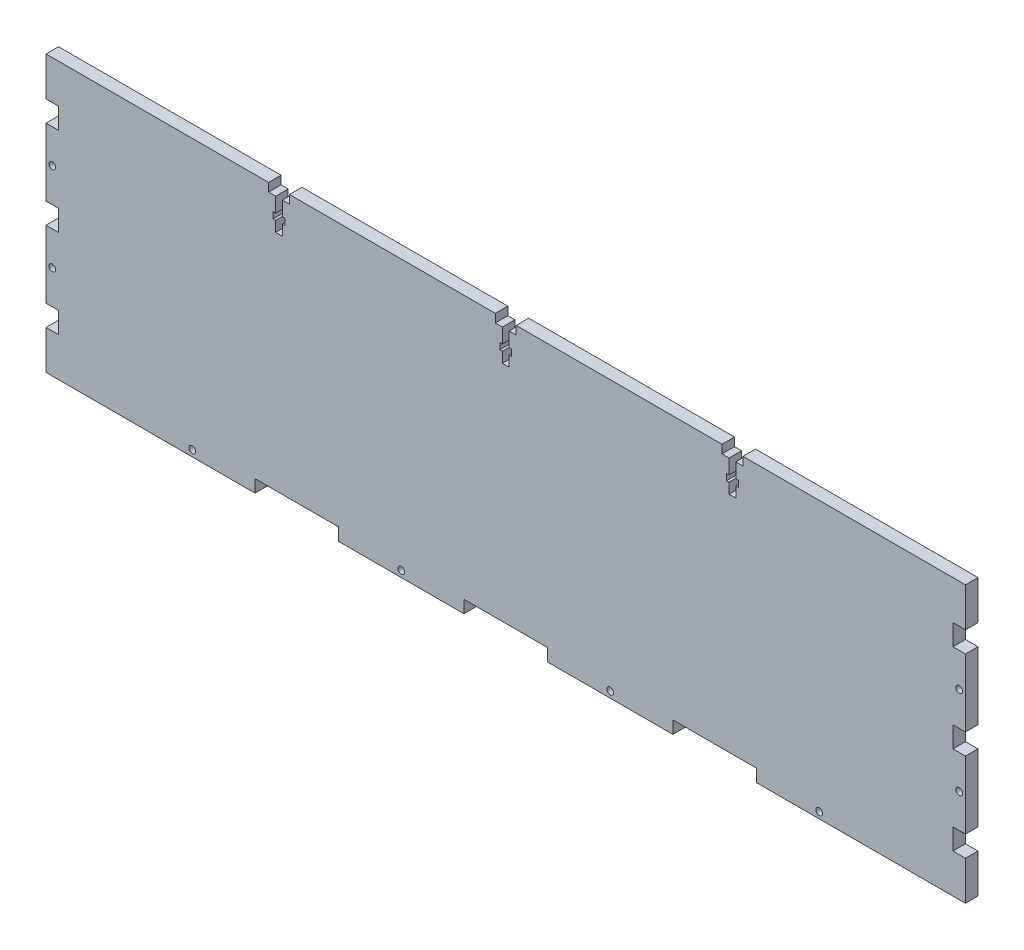
SolidWorks part; units mm, degrees
ref_plane "Front Plane" through (0, 0, 0) normal (0, 0, 1) x (1, 0, 0)
ref_plane "Top Plane" through (0, 0, 0) normal (0, 1, 0) x (1, 0, 0)
ref_plane "Right Plane" through (0, 0, 0) normal (1, 0, 0) x (0, 0, -1)
sketch "Sketch1" plane through (0, 0, 0) normal (0, 0, 1) x (1, 0, 0)
  line L1 (-220, -66) -> (220, -66)
  line L2 (-220, -66) -> (-220, 66)
  line L3 (-220, 66) -> (220, 66)
  line L4 (220, -66) -> (220, 66)
  line L5 (-220, -66) -> (220, 66) construction
  line L6 (-220, 66) -> (220, -66) construction
  point P0 (0, 0)
  dimension "D1" = 440
  dimension "D2" = 132
extrude "Boss-Extrude1" add sketch "Sketch1" along normal blind 6
sketch "Sketch2" plane through (0, 0, 0) normal (0, 0, -1) x (-1, 0, 0)
  line L0 (220, 47.3321) -> (220, 37.3321) construction
  line L1 (220, 37.3321) -> (214, 37.3321) construction
  line L2 (214, 37.3321) -> (214, 47.3321) construction
  line L3 (214, 47.3321) -> (220, 47.3321) construction
  line L12 (220, -37.3321) -> (220, -47.3321) construction
  line L13 (220, -47.3321) -> (214, -47.3321) construction
  line L14 (214, -47.3321) -> (214, -37.3321) construction
  line L15 (214, -37.3321) -> (220, -37.3321) construction
  line L16 (220, 47.3321) -> (220, 37.3321)
  line L17 (220, 37.3321) -> (214, 37.3321)
  line L18 (214, 37.3321) -> (214, 47.3321)
  line L19 (214, 47.3321) -> (220, 47.3321)
  line L20 (220, -37.3321) -> (220, -47.3321)
  line L21 (220, -47.3321) -> (214, -47.3321)
  line L22 (214, -47.3321) -> (214, -37.3321)
  line L23 (214, -37.3321) -> (220, -37.3321)
  line L24 (-214, -37.3321) -> (-214, -47.3321) construction
  line L25 (-214, -47.3321) -> (-220, -47.3321) construction
  line L26 (-220, -47.3321) -> (-220, -37.3321) construction
  line L27 (-220, -37.3321) -> (-214, -37.3321) construction
  line L28 (-214, 47.3321) -> (-214, 37.3321) construction
  line L29 (-214, 37.3321) -> (-220, 37.3321) construction
  line L30 (-220, 37.3321) -> (-220, 47.3321) construction
  line L31 (-220, 47.3321) -> (-214, 47.3321) construction
  line L32 (-214, -37.3321) -> (-214, -47.3321)
  line L33 (-214, -47.3321) -> (-220, -47.3321)
  line L34 (-220, -47.3321) -> (-220, -37.3321)
  line L35 (-220, -37.3321) -> (-214, -37.3321)
  line L36 (-214, 47.3321) -> (-214, 37.3321)
  line L37 (-214, 37.3321) -> (-220, 37.3321)
  line L38 (-220, 37.3321) -> (-220, 47.3321)
  line L39 (-220, 47.3321) -> (-214, 47.3321)
  line L44 (220, -5) -> (220, 5)
  line L45 (214, -5) -> (220, -5)
  line L46 (214, 5) -> (214, -5)
  line L47 (220, 5) -> (214, 5)
  line L48 (220, -5) -> (220, 5)
  line L49 (214, -5) -> (220, -5)
  line L50 (214, 5) -> (214, -5)
  line L51 (220, 5) -> (214, 5)
  line L52 (-214, -5) -> (-214, 5)
  line L53 (-220, -5) -> (-214, -5)
  line L54 (-220, 5) -> (-220, -5)
  line L55 (-214, 5) -> (-220, 5)
  line L56 (-214, -5) -> (-214, 5)
  line L57 (-220, -5) -> (-214, -5)
  line L58 (-220, 5) -> (-220, -5)
  line L59 (-214, 5) -> (-220, 5)
  circle A0 centre (217, 21.1661) radius 1.6 construction
  circle A1 centre (217, -21.1661) radius 1.6 construction
  circle A2 centre (-217, 21.1661) radius 1.6 construction
  circle A3 centre (-217, -21.1661) radius 1.6 construction
  circle A4 centre (217, 21.1661) radius 1.6
  circle A5 centre (217, -21.1661) radius 1.6
  circle A6 centre (-217, 21.1661) radius 1.6
  circle A7 centre (-217, -21.1661) radius 1.6
  dimension "D2" = 0
  dimension "D3" = 0
extrude "Cut-Extrude1" cut sketch "Sketch2" against normal up to next
sketch "Sketch3" plane through (0, 0, 0) normal (0, 0, -1) x (-1, 0, 0)
  circle A0 centre (-150, -63) radius 1.6 construction
  circle A1 centre (-50, -63) radius 1.6 construction
  circle A2 centre (50, -63) radius 1.6 construction
  circle A3 centre (150, -63) radius 1.6 construction
  circle A4 centre (-150, -63) radius 1.6
  circle A5 centre (-50, -63) radius 1.6
  circle A6 centre (50, -63) radius 1.6
  circle A7 centre (150, -63) radius 1.6
extrude "Cut-Extrude2" cut sketch "Sketch3" against normal up to next
sketch "Sketch4" plane through (0, 0, 0) normal (0, 0, -1) x (-1, 0, 0)
  line L0 (80, -66) -> (120, -66) construction
  line L1 (120, -66) -> (120, -60) construction
  line L2 (120, -60) -> (80, -60) construction
  line L3 (80, -60) -> (80, -66) construction
  line L4 (-20, -66) -> (20, -66) construction
  line L5 (20, -66) -> (20, -60) construction
  line L6 (20, -60) -> (-20, -60) construction
  line L7 (-20, -60) -> (-20, -66) construction
  line L8 (-120, -66) -> (-80, -66) construction
  line L9 (-80, -66) -> (-80, -60) construction
  line L10 (-80, -60) -> (-120, -60) construction
  line L11 (-120, -60) -> (-120, -66) construction
  line L12 (80, -66) -> (120, -66)
  line L13 (120, -66) -> (120, -60)
  line L14 (120, -60) -> (80, -60)
  line L15 (80, -60) -> (80, -66)
  line L16 (-20, -66) -> (20, -66)
  line L17 (20, -66) -> (20, -60)
  line L18 (20, -60) -> (-20, -60)
  line L19 (-20, -60) -> (-20, -66)
  line L20 (-120, -66) -> (-80, -66)
  line L21 (-80, -66) -> (-80, -60)
  line L22 (-80, -60) -> (-120, -60)
  line L23 (-120, -60) -> (-120, -66)
extrude "Cut-Extrude3" cut sketch "Sketch4" against normal up to next
sketch "Sketch5" plane through (0, 66, 0) normal (0, 1, 0) x (1, 0, 0)
  line L0 (220, 0) -> (-220, 0) construction
  line L1 (-113.5, -6) -> (-103.5, -6)
  line L2 (-113.5, -6) -> (-113.5, 0)
  line L3 (-113.5, 0) -> (-103.5, 0)
  line L4 (-103.5, -6) -> (-103.5, 0)
  line L5 (-113.5, -6) -> (-103.5, 0) construction
  line L6 (-113.5, 0) -> (-103.5, -6) construction
  line L7 (-103.5, -6) -> (-103.5, 0) construction
  line L8 (5, -6) -> (5, 0) construction
  line L9 (-5, -6) -> (5, -6)
  line L10 (-5, -6) -> (-5, 0)
  line L11 (-5, 0) -> (5, 0)
  line L12 (5, -6) -> (5, 0)
  line L13 (-5, -6) -> (5, 0) construction
  line L14 (-5, 0) -> (5, -6) construction
  line L15 (113.5, -6) -> (113.5, 0) construction
  line L16 (103.5, -6) -> (113.5, -6)
  line L17 (103.5, -6) -> (103.5, 0)
  line L18 (103.5, 0) -> (113.5, 0)
  line L19 (113.5, -6) -> (113.5, 0)
  line L20 (103.5, -6) -> (113.5, 0) construction
  line L21 (103.5, 0) -> (113.5, -6) construction
  point P0 (-108.5, -3)
  point P10 (0, -3)
  point P18 (108.5, -3)
extrude "Cut-Extrude4" cut sketch "Sketch5" against normal blind 4
sketch "Sketch6" plane through (0, 0, 0) normal (0, 0, -1) x (-1, 0, 0)
  line L0 (-108.5, 62) -> (-108.5, 47) construction
  line L1 (-113.5, 62) -> (-103.5, 62) construction
  line L2 (-110.1, 62) -> (-110.1, 55)
  line L3 (-106.9, 62) -> (-106.9, 55)
  line L4 (-110.1, 62) -> (-106.9, 62)
  line L5 (-110.1, 47) -> (-106.9, 47)
  line L6 (-106.9, 52) -> (-105.7, 52)
  line L7 (-111.3, 55) -> (-110.1, 55)
  line L8 (-111.3, 55) -> (-111.3, 52)
  line L9 (-111.3, 52) -> (-110.1, 52)
  line L10 (-105.7, 55) -> (-105.7, 52)
  line L11 (-111.3, 55) -> (-105.7, 52) construction
  line L12 (-111.3, 52) -> (-105.7, 55) construction
  line L13 (-106.9, 52) -> (-106.9, 47)
  line L14 (-106.9, 62) -> (-106.9, 47) construction
  line L15 (-110.1, 52) -> (-110.1, 47)
  line L16 (-110.1, 62) -> (-110.1, 47) construction
  line L17 (-106.9, 55) -> (-105.7, 55)
  line L18 (-1.6, 62) -> (-1.6, 55)
  line L19 (1.6, 62) -> (1.6, 55)
  line L20 (-1.6, 62) -> (1.6, 62)
  line L21 (-1.6, 47) -> (1.6, 47)
  line L22 (1.6, 52) -> (2.8, 52)
  line L23 (-2.8, 55) -> (-1.6, 55)
  line L24 (-2.8, 55) -> (-2.8, 52)
  line L25 (-2.8, 52) -> (-1.6, 52)
  line L26 (2.8, 55) -> (2.8, 52)
  line L27 (1.6, 52) -> (1.6, 47)
  line L28 (-1.6, 52) -> (-1.6, 47)
  line L29 (1.6, 55) -> (2.8, 55)
  line L30 (0, 62) -> (0, 47) construction
  line L31 (-2.8, 55) -> (2.8, 52) construction
  line L32 (-2.8, 52) -> (2.8, 55) construction
  line L33 (106.9, 62) -> (106.9, 55)
  line L34 (110.1, 62) -> (110.1, 55)
  line L35 (106.9, 62) -> (110.1, 62)
  line L36 (106.9, 47) -> (110.1, 47)
  line L37 (110.1, 52) -> (111.3, 52)
  line L38 (105.7, 55) -> (106.9, 55)
  line L39 (105.7, 55) -> (105.7, 52)
  line L40 (105.7, 52) -> (106.9, 52)
  line L41 (111.3, 55) -> (111.3, 52)
  line L42 (110.1, 52) -> (110.1, 47)
  line L43 (106.9, 52) -> (106.9, 47)
  line L44 (110.1, 55) -> (111.3, 55)
  line L45 (108.5, 62) -> (108.5, 47) construction
  line L46 (105.7, 55) -> (111.3, 52) construction
  line L47 (105.7, 52) -> (111.3, 55) construction
  point P8 (-108.5, 53.5)
  point P25 (0, 53.5)
  point P40 (108.5, 53.5)
  dimension "D1" = 15
  dimension "D4" = 5.6
  dimension "D5" = 3
  dimension "D6" = 7
  dimension "D2" = 1.6
  dimension "D3" = 1.6
  dimension "D7" = 3
extrude "Cut-Extrude5" cut sketch "Sketch6" against normal up to next
equation "\"m3_depth\"=15"
equation "\"D1@Sketch6\"=\"m3_depth\""
equation "\"m3_nut_width\"=5.6"
equation "\"D4@Sketch6\"=\"m3_nut_width\""
equation "\"m3_nut_thickness\"=3"
equation "\"D5@Sketch6\"=\"m3_nut_thickness\""
equation "\"m3_nut_depth\"=7"
equation "\"D6@Sketch6\"=\"m3_nut_depth\""
